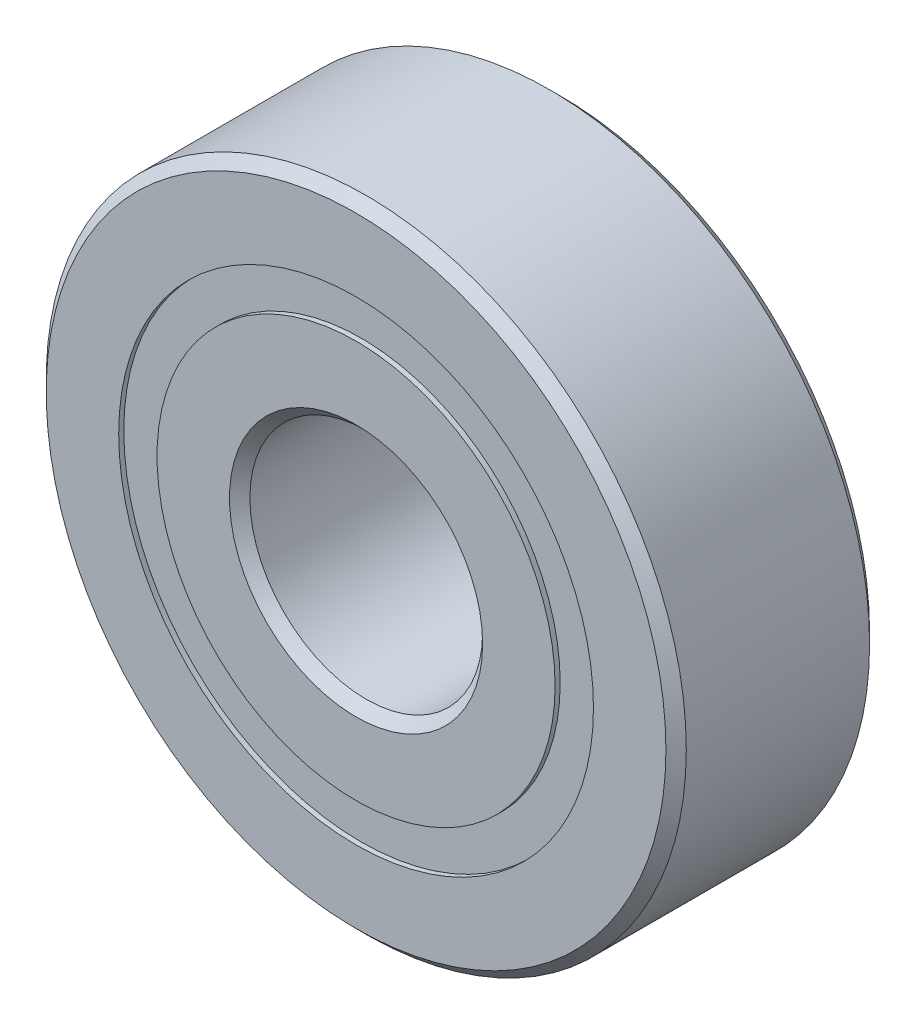
SolidWorks part; units mm, degrees
ref_plane "Front Plane" through (0, 0, 0) normal (0, 0, 1) x (1, 0, 0)
ref_plane "Top Plane" through (0, 0, 0) normal (0, 1, 0) x (1, 0, 0)
ref_plane "Right Plane" through (0, 0, 0) normal (1, 0, 0) x (0, 0, -1)
sketch "Sketch1" plane through (0, 0, 0) normal (1, 0, 0) x (0, 0, -1)
  line L0 (-3.5, 0) -> (3.5, 0) construction
  line L1 (0, 11) -> (0, -11) construction
  line L2 (3.15, 11) -> (-3.15, 11)
  line L3 (-3.15, 11) -> (-3.5, 10.65)
  line L4 (-3.5, 10.65) -> (-3.5, 8.1593)
  line L5 (-3.5, 8.1593) -> (-1.5556, 8.1593)
  line L6 (3.5, 8.1593) -> (1.5556, 8.1593)
  line L7 (3.5, 10.65) -> (3.5, 8.1593)
  line L8 (3.15, 11) -> (3.5, 10.65)
  line L9 (0, 11) -> (0, 7.5) construction
  line L10 (0, 7.5) -> (0, 4) construction
  arc A0 (-1.5556, 8.1593) -> (1.5556, 8.1593) centre (0, 7.5) cw
  point P14 (0, 4)
  dimension "D3" = 3.1111
  dimension "D1" = 45
  dimension "Width" = 7
  dimension "OD" = 22
  dimension "D2" = 0.35
  dimension "Shaft Dia" = 8
  dimension "D4" = 0.6593
revolve "Revolve1" add sketch "Sketch1" angle 360 about L0
sketch "Sketch3" plane through (0, 0, 0) normal (1, 0, 0) x (0, 0, -1)
  line L0 (-3.5, 6.8407) -> (-1.5556, 6.8407)
  line L1 (0, 11) -> (0, -11) construction
  line L2 (-3.5, 10.65) -> (-3.5, 8.1593) construction
  line L3 (-3.5, 6.8407) -> (-3.5, 4.35)
  line L4 (-3.15, 11) -> (-3.5, 10.65) construction
  line L5 (-3.5, 4.35) -> (-3.15, 4)
  line L6 (-3.15, 4) -> (3.15, 4)
  line L7 (3.15, 11) -> (3.15, -11) construction
  line L8 (3.15, 4) -> (3.5, 4.35)
  line L9 (3.5, -10.65) -> (3.5, 10.65) construction
  line L10 (3.5, 4.35) -> (3.5, 6.8407)
  line L11 (3.5, 6.8407) -> (1.5556, 6.8407)
  line L13 (3.15, 11) -> (3.5, 10.65) construction
  arc A0 (1.5556, 8.1593) -> (-1.5556, 8.1593) centre (0, 7.5) ccw construction
  arc A1 (1.5556, 6.8407) -> (-1.5556, 6.8407) centre (0, 7.5) cw
revolve "Revolve3" add sketch "Sketch3" angle 360 about L0
sketch "Sketch4" plane through (0, 0, 0) normal (1, 0, 0) x (0, 0, -1)
  line L0 (-1.6895, 7.5) -> (1.6895, 7.5)
  arc A2 (-1.6895, 7.5) -> (1.6895, 7.5) centre (0, 7.5) cw
  arc A3 (1.5556, 8.1593) -> (-1.5556, 8.1593) centre (0, 7.5) ccw construction
revolve "Revolve4" add sketch "Sketch4" angle 360 about L0
ref_axis "Axis1" through (0, 0, -3.5) along (0, 0, 1)
pattern_circular "CirPattern1" count 12 every 30 about axis through (0, 0, -3.5) along (0, 0, 1) of bodies 104
sketch "Sketch5" plane through (0, 0, 0) normal (1, 0, 0) x (0, 0, -1)
  line L0 (-3.5, 8.1593) -> (-1.5556, 8.1593) construction
  line L1 (-3.325, 8.1593) -> (-1.6895, 8.1593)
  line L2 (-3.325, 8.1593) -> (-3.325, 6.8407)
  line L3 (-3.325, 6.8407) -> (-1.6895, 6.8407)
  line L4 (-1.6895, 8.1593) -> (-1.6895, 6.8407)
  line L5 (-3.5, 6.8407) -> (-1.5556, 6.8407) construction
  line L6 (3.5, 8.1593) -> (1.5556, 8.1593) construction
  line L7 (3.325, 8.1593) -> (1.6895, 8.1593)
  line L8 (3.325, 8.1593) -> (3.325, 6.8407)
  line L9 (3.325, 6.8407) -> (1.6895, 6.8407)
  line L10 (1.6895, 8.1593) -> (1.6895, 6.8407)
  line L11 (3.5, 6.8407) -> (1.5556, 6.8407) construction
  line L12 (-3.15, 11) -> (-3.5, 10.65) construction
  point P18 (-3.325, 10.825)
revolve "Revolve5" add sketch "Sketch5" angle 360 about L0
equation "\"D2@Sketch1\" = \"Width@Sketch1\"*.05"
equation "\"D3@Sketch1\" = \"Width@Sketch1\"/2.25"
equation "\"D4@Sketch1\" = (((\"OD@Sketch1\"-\"Width@Sketch1\")/2)/3.25)/3.5"
equation "\"D2@CirPattern1\" = 360/\"Balls@CirPattern1\""
